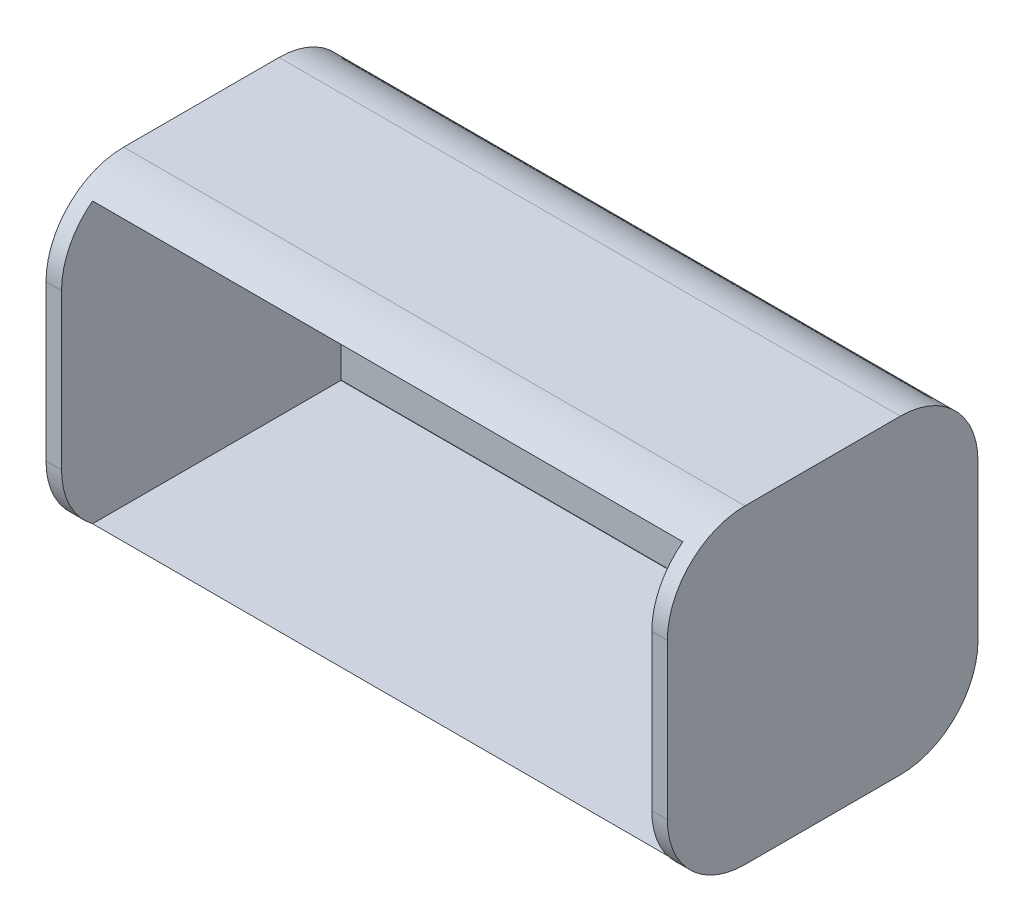
SolidWorks part; units mm, degrees
ref_plane "前视基准面" through (0, 0, 0) normal (0, 0, 1) x (1, 0, 0)
ref_plane "上视基准面" through (0, 0, 0) normal (0, 1, 0) x (1, 0, 0)
ref_plane "右视基准面" through (0, 0, 0) normal (1, 0, 0) x (0, 0, -1)
sketch "草图2" plane through (0, 0, 0) normal (0, 0, 1) x (1, 0, 0)
  line L1 (-100, -50) -> (100, -50)
  line L2 (-100, -50) -> (-100, 50)
  line L3 (-100, 50) -> (100, 50)
  line L4 (100, -50) -> (100, 50)
  line L5 (-100, -50) -> (100, 50) construction
  line L6 (-100, 50) -> (100, -50) construction
  point P0 (0, 0)
  dimension "D1" = 200
  dimension "D2" = 100
extrude "凸台-拉伸1" add sketch "草图2" along normal blind 100
sketch "草图3" plane through (0, 0, 100) normal (0, 0, 1) x (1, 0, 0)
  line L1 (-95, -45) -> (95, -45)
  line L2 (-95, -45) -> (-95, 45)
  line L3 (-95, 45) -> (95, 45)
  line L4 (95, -45) -> (95, 45)
  line L5 (-95, -45) -> (95, 45) construction
  line L6 (-95, 45) -> (95, -45) construction
  point P0 (0, 0)
  dimension "D1" = 190
  dimension "D2" = 90
extrude "切除-拉伸1" cut sketch "草图3" against normal blind 90
fillet "圆角1" radius 25 4 edges at (0, 50, 0) (0, -50, 100) (0, -50, 0) (0, 50, 100)
sketch "草图4" plane through (-100, 0, 0) normal (-1, 0, 0) x (0, 0, 1)
  line L0 (0, 0) -> (12.8132, 0) construction
  line L1 (50, 0) -> (50, 4.5986) construction
  line L2 (50, 4.5986) -> (50, -3.9179) construction
  line L3 (100, -25) -> (100, 25) construction
  circle A4 centre (50, 0) radius 2
  dimension "D2" = 4
  dimension "D1" = 50
extrude "凸台-拉伸2" add sketch "草图4" along normal blind 10
